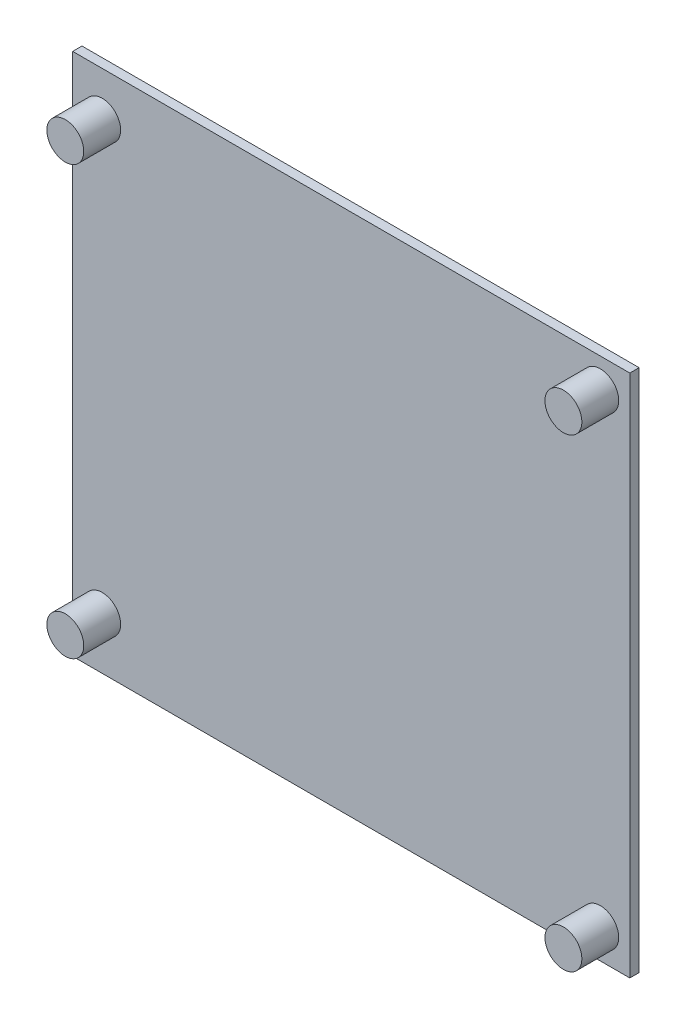
SolidWorks part; units mm, degrees
ref_plane "Front" through (0, 0, 0) normal (0, 0, 1) x (1, 0, 0)
ref_plane "Top" through (0, 0, 0) normal (0, 1, 0) x (1, 0, 0)
ref_plane "Right" through (0, 0, 0) normal (1, 0, 0) x (0, 0, -1)
sketch "Sketch1" plane through (0, 0, 0) normal (0, 0, 1) x (1, 0, 0)
  line L1 (-47.9425, 45.085) -> (47.9425, 45.085)
  line L2 (-47.9425, 45.085) -> (-47.9425, -45.085)
  line L3 (-47.9425, -45.085) -> (47.9425, -45.085)
  line L4 (47.9425, 45.085) -> (47.9425, -45.085)
  line L5 (-47.9425, 45.085) -> (47.9425, -45.085) construction
  line L6 (-47.9425, -45.085) -> (47.9425, 45.085) construction
  circle A0 centre (42.8625, -40.005) radius 3.175
  circle A1 centre (-42.8625, -36.195) radius 3.175
  circle A2 centre (-42.8625, 37.465) radius 3.175
  circle A3 centre (42.8625, 40.005) radius 3.175
  point P0 (0, 0)
  dimension "D3" = 6.35
  dimension "D4" = 6.35
  dimension "D5" = 6.35
  dimension "D6" = 6.35
  dimension "D7" = 5.08
  dimension "D8" = 5.08
  dimension "D9" = 5.08
  dimension "D11" = 7.62
  dimension "D12" = 8.89
  dimension "D13" = 5.08
  dimension "D14" = 5.08
  dimension "D1" = 95.885
  dimension "D2" = 90.17
  dimension "D10" = 5.08
extrude "Boss-Extrude1" add sketch "Sketch1" along normal blind 1.6
extrude "Boss-Extrude2" add sketch "Sketch1<3>" along normal blind 7.95 and the other way blind 0.4 contours A3 | A1 | A0 | A2 region at (42.8625, -40.005, 0) region at (-42.8625, -36.195, 0) region at (42.8625, 40.005, 0)
sketch "Sketch1<3>" plane through (0, 0, 0) normal (0, 0, 1) x (1, 0, 0) same geometry as "Sketch1"
